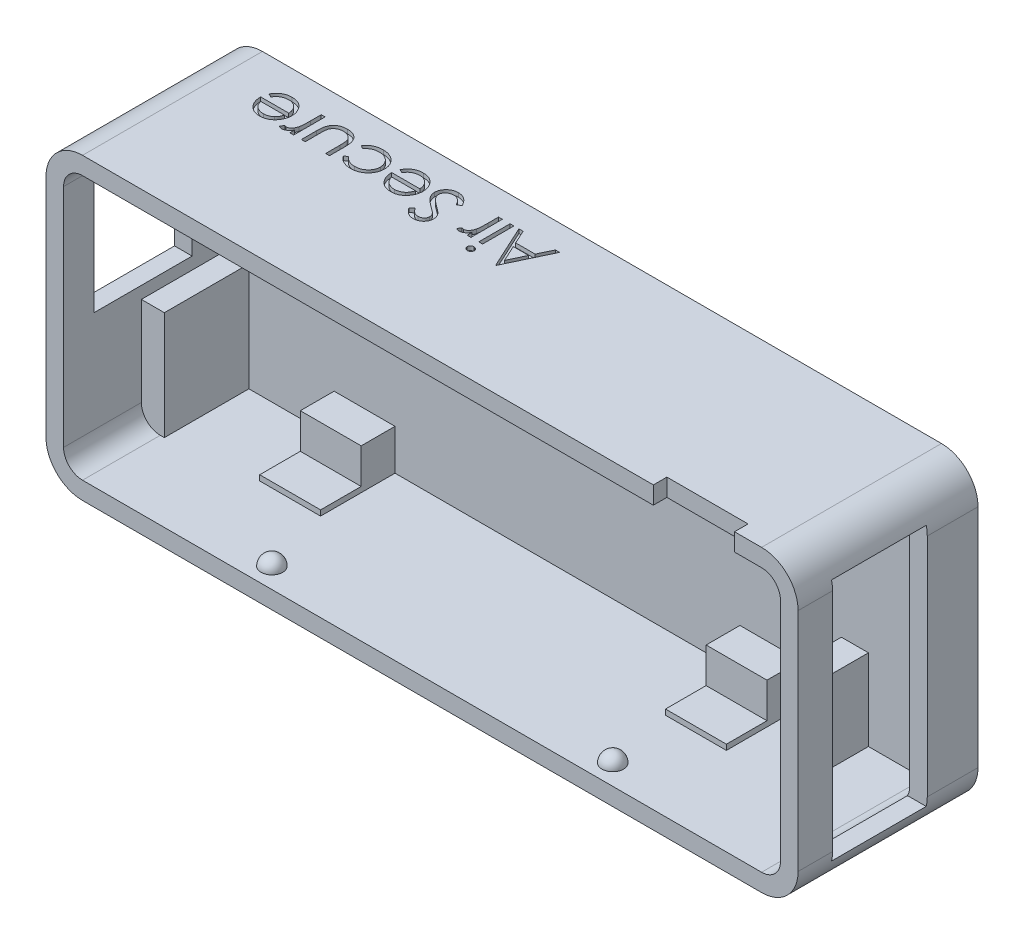
SolidWorks part; units mm, degrees
material "PLA"
ref_plane "Front Plane" through (0, 0, 0) normal (0, 0, 1) x (1, 0, 0)
ref_plane "Top Plane" through (0, 0, 0) normal (0, 1, 0) x (1, 0, 0)
ref_plane "Right Plane" through (0, 0, 0) normal (1, 0, 0) x (0, 0, -1)
sketch "Sketch2" plane through (0, 0, 0) normal (0, 0, 1) x (1, 0, 0)
  line L1 (2.4, -42.153) -> (-47.8, -42.153)
  line L2 (3.8, -43.553) -> (3.8, -60.253)
  line L3 (2.4, -61.653) -> (-47.8, -61.653)
  line L4 (-49.2, -43.553) -> (-49.2, -60.253)
  arc A0 (3.8, -43.553) -> (2.4, -42.153) centre (2.4, -43.553) ccw
  arc A1 (2.4, -61.653) -> (3.8, -60.253) centre (2.4, -60.253) ccw
  arc A2 (-49.2, -60.253) -> (-47.8, -61.653) centre (-47.8, -60.253) ccw
  arc A3 (-49.2, -43.553) -> (-47.8, -42.153) centre (-47.8, -43.553) cw
  point P2 (3.8, -42.153)
  point P9 (-49.2, -61.653)
  point P14 (-49.2, -42.153)
  dimension "D1" = 19.5
  dimension "D3" = 1.4
  dimension "D2" = 53
extrude "Boss-Extrude1" add sketch "Sketch2" along normal blind 12 contours L2 A1 L3 A2 L4 A3 L1 A0
shell "Shell1" thickness 1.3 removed face at (-22.7, -51.903, 12) outward yes
sketch "Sketch3" plane through (0, -61.653, 0) normal (0, 1, 0) x (1, 0, 0)
  line L0 (-10.9, -10.5) -> (-9.3, -10.5)
  line L1 (2.4, -12) -> (-47.8, -12) construction
  line L3 (3.8, -12) -> (3.8, 0) construction
  arc A0 (-9.3, -10.5) -> (-10.9, -10.5) centre (-10.1, -10.5) ccw
  dimension "D4" = 0.8
  dimension "D1" = 1.5
  dimension "D2" = 13.9
  dimension "D3" = 1.6
revolve "Revolve1" add sketch "Sketch3" angle 360 about L0
ref_plane "Plane1" through (0, -51.903, 0) normal (0, 1, 0) x (1, 0, 0)
mirror "Mirror1" about plane through (0, -51.903, 0) normal (0, 1, 0) of "Revolve1"
sketch "Sketch9" plane through (0, 0, 0) normal (0, 0, 1) x (1, 0, 0)
  line L0 (-47.5, -61.653) -> (-47.5, -53.653)
  line L1 (2.4, -61.653) -> (-47.8, -61.653) construction
  line L2 (2.4, -42.153) -> (-47.8, -42.153) construction
  line L3 (-49.2, -43.553) -> (-49.2, -60.253) construction
  line L4 (-47.5, -53.653) -> (-49.2, -53.653)
  line L8 (2.4, -42.153) -> (-47.8, -42.153)
  line L9 (-49.2, -43.553) -> (-49.2, -60.253)
  line L10 (-47.8, -61.653) -> (2.4, -61.653)
  line L11 (3.8, -60.253) -> (3.8, -43.553)
  line L12 (-47.2, -42.153) -> (-47.8, -42.153)
  line L13 (-49.2, -43.553) -> (-49.2, -60.253)
  line L14 (-47.8, -61.653) -> (-47.5, -61.653)
  arc A4 (3.8, -43.553) -> (2.4, -42.153) centre (2.4, -43.553) ccw
  arc A5 (-47.8, -42.153) -> (-49.2, -43.553) centre (-47.8, -43.553) ccw
  arc A6 (-49.2, -60.253) -> (-47.8, -61.653) centre (-47.8, -60.253) ccw
  arc A7 (2.4, -61.653) -> (3.8, -60.253) centre (2.4, -60.253) ccw
  arc A9 (-47.8, -42.153) -> (-49.2, -43.553) centre (-47.8, -43.553) ccw
  arc A10 (-49.2, -60.253) -> (-47.8, -61.653) centre (-47.8, -60.253) ccw
  line M4 (-49.2, -43.553) -> (-49.2, -60.253)
  arc M5 (-49.2, -60.253) -> (-47.8, -61.653) centre (-47.8, -60.253) ccw
  line M6 (-47.8, -61.653) -> (2.4, -61.653)
  dimension "D1" = 1.7
  dimension "D3" = 8
  dimension "D2" = 0
extrude "Boss-Extrude3" add sketch "Sketch9" along normal blind 6.25 contours L0 L4 M4 M5 M6 region at (-48.3329, -57.5354, 0)
sketch "Sketch10" plane through (5.1, 0, 0) normal (1, 0, 0) x (0, 0, -1)
  line L0 (6.6, -51.903) -> (-6.6, -51.903) construction
  line L1 (-2.45, -60.903) -> (-9.45, -60.903)
  line L2 (-2.45, -60.903) -> (-2.45, -42.903)
  line L3 (-2.45, -42.903) -> (-9.45, -42.903)
  line L4 (-9.45, -60.903) -> (-9.45, -42.903)
  line L5 (-2.45, -60.903) -> (-9.45, -42.903) construction
  line L6 (-2.45, -42.903) -> (-9.45, -60.903) construction
  line L7 (1.3, -43.553) -> (1.3, -60.253) construction
  point P0 (-5.95, -51.903)
  dimension "D1" = 0
  dimension "D2" = 3.75
  dimension "D3" = 18
  dimension "D4" = 7
extrude "Cut-Extrude1" cut sketch "Sketch10" against normal blind 2.7
sketch "Sketch11" plane through (0, 0, 0) normal (0, 0, 1) x (1, 0, 0)
  line L0 (6.6, -51.903) -> (-6.6, -51.903) construction
  line L1 (-1.7, -61.653) -> (-3.7, -61.653)
  line L2 (-1.7, -61.653) -> (-1.7, -55.653)
  line L3 (-1.7, -42.153) -> (-3.7, -42.153)
  line L4 (-3.7, -61.653) -> (-3.7, -55.653)
  line L5 (-1.7, -61.653) -> (-3.7, -42.153) construction
  line L6 (-1.7, -42.153) -> (-3.7, -61.653) construction
  line L7 (-1.7, -48.153) -> (-3.7, -48.153)
  line L9 (-1.7, -55.653) -> (-3.7, -55.653)
  line L10 (-1.7, -48.153) -> (-1.7, -42.153)
  line L11 (-3.7, -48.153) -> (-3.7, -42.153)
  line L12 (-49.2, -43.553) -> (-49.2, -53.653) construction
  point P0 (-2.7, -51.903)
  dimension "D1" = 0
  dimension "D2" = 46.5
  dimension "D3" = 2
  dimension "D4" = 19.5
  dimension "D5" = 6
  dimension "D6" = 6
extrude "Boss-Extrude4" add sketch "Sketch11" along normal blind 4
ref_plane "Plane2" through (-22.7, 0, 0) normal (-1, 0, 0) x (0, 0, 1)
mirror "Mirror3" about plane through (-22.7, 0, 0) normal (-1, 0, 0) of "Revolve1", "Mirror1"
sketch "Sketch12" plane through (0, 0, 0) normal (0, 0, 1) x (1, 0, 0)
  line L0 (-3.7, -61.653) -> (-47.5, -61.653) construction
  line L1 (-6.7, -61.653) -> (-11.2, -61.653)
  line L2 (-6.7, -61.653) -> (-6.7, -58.653)
  line L3 (-6.7, -58.653) -> (-11.2, -58.653)
  line L4 (-11.2, -61.653) -> (-11.2, -58.653)
  line L5 (-3.7, -55.653) -> (-3.7, -61.653) construction
  dimension "D1" = 3
  dimension "D2" = 4.5
  dimension "D3" = 3
extrude "Boss-Extrude5" add sketch "Sketch12" along normal blind 2.5
sketch "Sketch27" plane through (0, 0, 2.5) normal (0, 0, 1) x (1, 0, 0)
  line L0 (-11.2, -61.653) -> (-6.7, -61.653) construction
  line L1 (-6.7, -61.653) -> (-11.2, -61.653)
  line L2 (-6.7, -61.653) -> (-6.7, -61.253)
  line L3 (-6.7, -61.253) -> (-11.2, -61.253)
  line L4 (-11.2, -61.653) -> (-11.2, -61.253)
  line L5 (-6.7, -61.653) -> (-6.7, -58.653) construction
  line L6 (-11.2, -58.653) -> (-11.2, -61.653) construction
  dimension "D1" = 0.4
extrude "Boss-Extrude6" add sketch "Sketch27" along normal blind 3
pattern_linear "LPattern1" count 2 spacing 30 along (-1, 0, 0) of "Boss-Extrude5", "Boss-Extrude6"
sketch "Sketch19" plane through (0, -40.853, 0) normal (0, 1, 0) x (1, 0, 0)
  line L0 (-23.7888, -0.576) -> (-45.0839, -0.576) construction
  text T0 "Air Secure"
extrude "Cut-Extrude4" cut sketch "Sketch19" against normal blind 0.3
sketch "Sketch21" plane through (0, -62.953, 0) normal (0, -1, 0) x (1, 0, 0)
  line L0 (-45.043, 0.6352) -> (0, 0.6352) construction
  text T0 "Air Secure"
extrude "Cut-Extrude5" cut sketch "Sketch21" against normal blind 0.3
sketch "Sketch22" plane through (0, 0, -1.3) normal (0, 0, -1) x (-1, 0, 0)
  line L1 (3.7, -55.653) -> (3.7, -61.653) construction
  circle A0 centre (11.7, -51.9812) radius 1.75
  dimension "D2" = 3.5
  dimension "D1" = 8
extrude "Cut-Extrude6" [suppressed] cut sketch "Sketch22" against normal blind 1.3
pattern_linear "LPattern2" [suppressed] count 4 spacing 10 of bodies 114
sketch "Sketch23" plane through (-50.5, 0, 0) normal (-1, 0, 0) x (0, 0, 1)
  line L0 (12, -43.553) -> (12, -60.253) construction
  line L2 (12, -61.653) -> (6.25, -61.653) construction
  circle A0 centre (5.5, -51.903) radius 1.75
  dimension "D3" = 3.5
  dimension "D1" = 6.5
  dimension "D2" = 9.75
extrude "Cut-Extrude7" [suppressed] cut sketch "Sketch23" against normal blind 1.3
sketch "Sketch24" plane through (0, -40.853, 0) normal (0, 1, 0) x (1, 0, 0)
  line L0 (2.4, -12) -> (2.4, 1.3) construction
  line L1 (2.4, -12) -> (-47.8, -12) construction
  circle A0 centre (-7.6, -6) radius 1.25
  dimension "D1" = 2.5
  dimension "D2" = 10
  dimension "D3" = 6
extrude "Cut-Extrude8" [suppressed] cut sketch "Sketch24" against normal blind 1.3
pattern_linear "LPattern3" [suppressed] count 4 spacing 10 count 2 spacing 20.8 of bodies 117
sketch "Sketch25" plane through (0, -40.853, 0) normal (0, 1, 0) x (1, 0, 0)
  line L0 (2.4, -12) -> (-47.8, -12) construction
  line L1 (0.4, -12) -> (-5.6, -12)
  line L2 (0.4, -12) -> (0.4, -11)
  line L3 (0.4, -11) -> (-5.6, -11)
  line L4 (-5.6, -12) -> (-5.6, -11)
  line L5 (2.4, -12) -> (2.4, 1.3) construction
  dimension "D1" = 2
  dimension "D2" = 1
  dimension "D3" = 6
extrude "Cut-Extrude9" cut sketch "Sketch25" against normal blind 10
mirror "Mirror2" [suppressed] about plane through (0, -51.903, 0) normal (0, 1, 0)
sketch "Sketch26" plane through (-50.5, 0, 0) normal (-1, 0, 0) x (0, 0, 1)
  line L0 (-1.3, -43.553) -> (-1.3, -60.253) construction
  line L1 (9.75, -52.753) -> (2.5, -52.753)
  line L2 (9.75, -52.753) -> (9.75, -42.753)
  line L3 (9.75, -42.753) -> (2.5, -42.753)
  line L4 (2.5, -52.753) -> (2.5, -42.753)
  line L5 (12, -40.853) -> (-1.3, -40.853) construction
  dimension "D1" = 10
  dimension "D2" = 3.8
  dimension "D3" = 7.25
  dimension "D4" = 1.9
extrude "Cut-Extrude10" cut sketch "Sketch26" against normal blind 4
mirror "Mirror4" about plane through (0, -51.903, 0) normal (0, 1, 0) of "Boss-Extrude5", "Boss-Extrude6", "LPattern1"
equation "\"D1@Boss-Extrude1\" = \"BoxDepth\"'depth"
equation "\"D1@Shell1\"=\"WallThickness\""
equation "\"BoxWidth\"= 19.5mm'inner width"
equation "\"D1@Sketch2\"=\"BoxWidth\""
equation "\"BoxLength\"= 53mm'inner length"
equation "\"D2@Sketch2\"=\"BoxLength\""
equation "\"D3@Sketch2\" = \"CornerRadius\"'inner corner radius"
equation "\"CornerRadius\"= 1.4mm'inner corner radius"
equation "\"BoxDepth\"= 12mm'inner depth"
equation "\"WallThickness\"= 1.3mm"
equation "\"LatchOffEdge\"= 1.5mm"
equation "\"LatchRadius\"= 0.8mm"
equation "\"D2@Sketch3\"=(\"BoxLength\"+\"WallThickness\"*2)/4"
equation "\"D1@Sketch3\"=\"LatchOffEdge\""
equation "\"D3@Sketch3\"=\"LatchRadius\"*2"
equation "\"D4@Sketch3\"=\"LatchRadius\""
equation "\"PortWidth\"= 18mm"
equation "\"PortHeight\"= 7mm"
equation "\"PortOffsetBottom\"= 3.75mm"
equation "\"D3@Sketch10\"=\"PortWidth\""
equation "\"D2@Sketch10\"=\"PortOffsetBottom\""
equation "\"D4@Sketch10\"=\"PortHeight\""
equation "\"D1@Cut-Extrude1\"=\"WallThickness\"+\"CornerRadius\""
equation "\"D4@Sketch11\"=\"BoxWidth\""
equation "\"D4@LPattern1\"=\"BoxWidth\"-\"D1@Sketch12\""
equation "\"D1@Cut-Extrude6\"=\"WallThickness\""
equation "\"D2@Sketch23\"=\"BoxWidth\"/2"
equation "\"D1@Cut-Extrude7\"=\"WallThickness\""
equation "\"D1@Cut-Extrude8\"=\"WallThickness\""
equation "\"D4@LPattern3\"=\"BoxWidth\"+\"WallThickness\""
